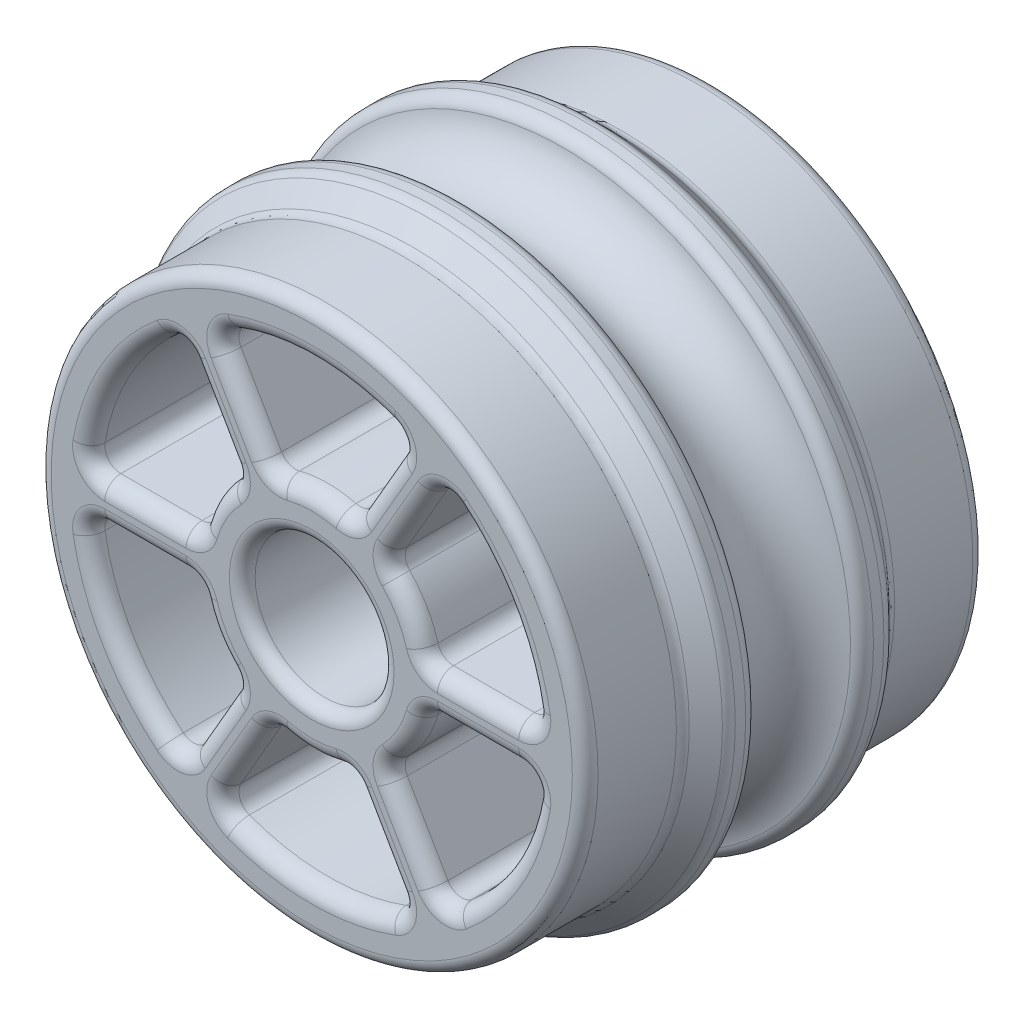
SolidWorks part; units mm, degrees
material "ABS"
ref_plane "Front Plane" through (0, 0, 0) normal (0, 0, 1) x (1, 0, 0)
ref_plane "Top Plane" through (0, 0, 0) normal (0, 1, 0) x (1, 0, 0)
ref_plane "Right Plane" through (0, 0, 0) normal (1, 0, 0) x (0, 0, -1)
sketch "Sketch1" plane through (0, 0, 0) normal (1, 0, 0) x (0, 0, -1)
  line L0 (-12.45, 4.318) -> (12.45, 4.318)
  line L1 (12.45, 4.318) -> (12.45, 17)
  line L2 (12.45, 17) -> (4.45, 17)
  line L3 (4.45, 17) -> (4.45, 18.5)
  line L4 (4.45, 18.5) -> (3.25, 18.5)
  line L5 (-3.25, 18.5) -> (-4.45, 18.5)
  line L6 (-4.45, 18.5) -> (-4.45, 17)
  line L7 (-4.45, 17) -> (-12.45, 17)
  line L8 (-12.45, 17) -> (-12.45, 4.318)
  line L9 (0, 0) -> (-29.3634, 0) construction
  arc A0 (3.25, 18.5) -> (-3.25, 18.5) centre (0, 18.5) cw
  point P0 (0, 4.318)
  dimension "D1" = 4.318
  dimension "D4" = 18.5
  dimension "D2" = 8
  dimension "D3" = 17
  dimension "D5" = 1.2
  dimension "D6" = 6.5
revolve "Revolve1" add sketch "Sketch1" angle 360 about L9
chamfer "Chamfer1" distance 2 angle 45 2 edges at (-17, 0, -4.45) (-17, 0, 4.45)
sketch "Sketch2" plane through (0, 0, 12.45) normal (0, 0, 1) x (1, 0, 0)
  line L0 (0, 0) -> (-7.625, 13.2069) construction
  line L1 (0, 0) -> (7.625, 13.2069) construction
  line L2 (-2.4688, 6.6761) -> (-5.9601, 12.7232)
  line L3 (2.4688, 6.6761) -> (5.9601, 12.7232)
  line L4 (0, 2.4) -> (-5.9601, 12.7232) construction
  line L5 (0, 2.4) -> (5.9601, 12.7232) construction
  arc A0 (-7.625, 13.2069) -> (7.625, 13.2069) centre (0, 0) cw construction
  circle A1 centre (0, 0) radius 15.25 construction
  arc A2 (-5.9601, 12.7232) -> (5.9601, 12.7232) centre (0, 0) cw
  circle A5 centre (0, 0) radius 7.118
  arc A6 (2.4688, 6.6761) -> (-2.4688, 6.6761) centre (0, 0) ccw
  point P7 (0, 0)
  dimension "D1" = 60
  dimension "D2" = 1.2
  dimension "D3" = 2.8
extrude "Cut-Extrude1" cut sketch "Sketch2" against normal through all
pattern_circular "CirPattern1" count 6 over 360 about axis through (0, 0, 0) along (0, 0, -1) of "Cut-Extrude1"
fillet "Fillet1" radius 1 72 edges at (-10.5074, 1.2, -12.45) (-10.5074, 1.2, 12.45) (-6.2929, 8.4997, -12.45) (-6.2929, 8.4997, 12.45) (-6.2929, -8.4997, -12.45) (-6.2929, -8.4997, 12.45) (-10.5074, -1.2, -12.45) (-10.5074, -1.2, 12.45) (4.2145, -9.6997, -12.45) (4.2145, -9.6997, 12.45) (-4.2145, -9.6997, -12.45) (-4.2145, -9.6997, 12.45) (10.5074, -1.2, -12.45) (10.5074, -1.2, 12.45) (6.2929, -8.4997, -12.45) (6.2929, -8.4997, 12.45) (6.2929, 8.4997, -12.45) (6.2929, 8.4997, 12.45) (10.5074, 1.2, -12.45) (10.5074, 1.2, 12.45) (4.2145, 9.6997, -12.45) (4.2145, 9.6997, 12.45) (-4.2145, 9.6997, -12.45) (-4.2145, 9.6997, 12.45) (-5.9601, -12.7232, 0) (0, -14.05, -12.45) (5.9601, -12.7232, 0) (0, -14.05, 12.45) (-8.0386, 11.5232, 0) (-12.1677, 7.025, -12.45) (-13.9987, 1.2, 0) (-12.1677, 7.025, 12.45) (-13.9987, -1.2, 0) (-12.1677, -7.025, -12.45) (-8.0386, -11.5232, 0) (-12.1677, -7.025, 12.45) (8.0386, -11.5232, 0) (12.1677, -7.025, -12.45) (13.9987, -1.2, 0) (12.1677, -7.025, 12.45) (13.9987, 1.2, 0) (12.1677, 7.025, -12.45) (8.0386, 11.5232, 0) (12.1677, 7.025, 12.45) (-2.4688, 6.6761, 0) (0, 7.118, -12.45) (2.4688, 6.6761, 0) (0, 7.118, 12.45) (-7.0161, 1.2, 0) (-6.1644, 3.559, -12.45) (-4.5473, 5.4761, 0) (-6.1644, 3.559, 12.45) (-4.5473, -5.4761, 0) (-6.1644, -3.559, -12.45) (-7.0161, -1.2, 0) (-6.1644, -3.559, 12.45) (2.4688, -6.6761, 0) (0, -7.118, -12.45) (-2.4688, -6.6761, 0) (0, -7.118, 12.45) (7.0161, -1.2, 0) (6.1644, -3.559, -12.45) (4.5473, -5.4761, 0) (6.1644, -3.559, 12.45) (4.5473, 5.4761, 0) (6.1644, 3.559, -12.45) (7.0161, 1.2, 0) (6.1644, 3.559, 12.45) (5.9601, 12.7232, 0) (0, 14.05, -12.45) (-5.9601, 12.7232, 0) (0, 14.05, 12.45)
fillet "Fillet2" radius 0.8 6 edges at (-17, 0, -6.45) (18.5, 0, -4.95) (-18.5, 0, -3.25) (-18.5, 0, 3.25) (-18.5, 0, 4.95) (17, 0, 6.45)
fillet "Fillet3" radius 0.8 2 edges at (-4.318, 0, -12.45) (-4.318, 0, 12.45)
fillet "Fillet4" radius 0.8 2 edges at (-17, 0, -12.45) (-17, 0, 12.45)
